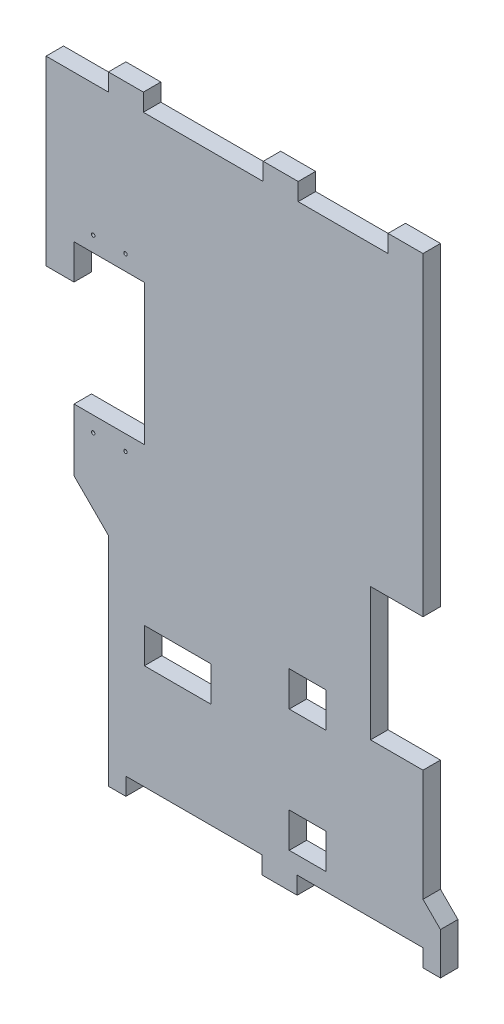
SolidWorks part; units mm, degrees
material "Balsa"
ref_plane "Plan de face" through (0, 0, 0) normal (0, 0, 1) x (1, 0, 0)
ref_plane "Plan de dessus" through (0, 0, 0) normal (0, 1, 0) x (1, 0, 0)
ref_plane "Plan de droite" through (0, 0, 0) normal (1, 0, 0) x (0, 0, -1)
sketch "Esquisse1" plane through (0, 0, 0) normal (0, 0, 1) x (1, 0, 0)
  line L0 (90, 82) -> (90, 167)
  line L1 (5, 0) -> (90, 0)
  line L2 (0, 0) -> (0, 167)
  line L3 (10, 167) -> (80, 167)
  line L4 (90, 0) -> (90, 44)
  line L5 (90, 82) -> (75, 82)
  line L6 (0, 167) -> (0, 172)
  line L7 (0, 172) -> (10, 172)
  line L8 (10, 167) -> (10, 172)
  line L9 (0, 0) -> (0, -5)
  line L10 (90, 167) -> (90, 172)
  line L11 (90, 172) -> (80, 172)
  line L12 (80, 167) -> (80, 172)
  line L13 (0, -5) -> (5, -5)
  line L14 (5, 0) -> (5, -5)
  line L16 (90, 44) -> (75, 44)
  line L17 (75, 82) -> (75, 44)
  line L18 (51.7344, 50) -> (62.2003, 50)
  line L19 (51.7344, 50) -> (51.7344, 40)
  line L20 (51.7344, 40) -> (62.2003, 40)
  line L25 (62.2003, 50) -> (62.2003, 40)
  line L32 (51.7344, 15) -> (62.2003, 15)
  line L34 (51.7344, 15) -> (51.7344, 5)
  line L35 (51.7344, 5) -> (62.2003, 5)
  line L37 (62.2003, 15) -> (62.2003, 5)
  line L54 (29.3073, 40) -> (10.2917, 40)
  line L55 (29.3073, 40) -> (29.3073, 30)
  line L56 (29.3073, 30) -> (10.2917, 30)
  line L57 (10.2917, 40) -> (10.2917, 30)
  dimension "D1" = 167
  dimension "D2" = 90
  dimension "D3" = 10
  dimension "D4" = 5
  dimension "D5" = 5
  dimension "D6" = 15
  dimension "D7" = 38
  dimension "D8" = 82
extrude "Boss.-Extru.1" add sketch "Esquisse1" along normal blind 5
sketch "Esquisse2" plane through (0, 0, 5) normal (0, 0, 1) x (1, 0, 0)
  line L0 (0, 172) -> (0, -5) construction
  line L1 (0, 167) -> (-9.8347, 167)
  line L2 (0, 167) -> (0, 57.1653)
  line L3 (0, 57.1653) -> (-9.8347, 67)
  line L4 (-9.8347, 167) -> (-9.8347, 67)
  line L6 (80, 167) -> (10, 167) construction
  dimension "D1" = 9.8347
  dimension "D2" = 135
  dimension "D3" = 100
extrude "Boss.-Extru.2" add sketch "Esquisse2" against normal blind 5
sketch "Esquisse3" plane through (0, 0, 0) normal (0, 0, -1) x (-1, 0, 0)
  line L0 (9.8347, 167) -> (9.8347, 67) construction
  line L1 (-10.3653, 125) -> (9.8347, 125)
  line L2 (-10.3653, 125) -> (-10.3653, 84.8)
  line L3 (-10.3653, 84.8) -> (9.8347, 84.8)
  line L4 (9.8347, 125) -> (9.8347, 84.8)
  line L5 (0, 167) -> (9.8347, 167) construction
  line L6 (4.3597, 129.4) -> (-4.8903, 129.4) construction
  line L7 (-4.8903, 129.4) -> (-4.8903, 80.4) construction
  line L8 (-4.8903, 80.4) -> (4.3597, 80.4) construction
  line L9 (9.8347, 167) -> (9.8347, 67) construction
  line L10 (-80, 167) -> (-10, 167) construction
  circle A0 centre (4.3597, 129.4) radius 0.5
  circle A1 centre (-4.8903, 129.4) radius 0.5
  circle A2 centre (4.3597, 80.4) radius 0.5
  circle A3 centre (-4.8903, 80.4) radius 0.5
  dimension "D9" = 1
  dimension "D1" = 17.8
  dimension "D2" = 42
  dimension "D3" = 20.2
  dimension "D4" = 9.25
  dimension "D5" = 9.25
  dimension "D6" = 49
  dimension "D7" = 14.725
  dimension "D8" = 37.6
extrude "Enlèv. mat.-Extru.1" cut sketch "Esquisse3" against normal blind 5
sketch "Esquisse4" plane through (0, 0, 5) normal (0, 0, 1) x (1, 0, 0)
  line L0 (-9.8347, 167) -> (-17.8347, 167)
  line L1 (-9.8347, 167) -> (-9.8347, 125) construction
  line L2 (-17.8347, 167) -> (-17.8347, 115)
  line L3 (-17.8347, 115) -> (-9.8347, 115)
  line L4 (-9.8347, 115) -> (-9.8347, 125)
  line L5 (-9.8347, 125) -> (-9.8347, 167)
  line L6 (0, 167) -> (-9.8347, 167) construction
  line L7 (5, 0) -> (90, 0) construction
  line L8 (44, 0) -> (54, 0)
  line L9 (44, 0) -> (44, -5)
  line L10 (44, -5) -> (54, -5)
  line L11 (54, 0) -> (54, -5)
  line L12 (0, 57.1653) -> (0, -5) construction
  line L13 (90, 0) -> (90, 44) construction
  line L14 (90, 12) -> (95, 7)
  line L15 (90, 12) -> (90, -5)
  line L16 (90, -5) -> (95, -5)
  line L17 (95, 7) -> (95, -5)
  line L18 (80, 167) -> (10, 167) construction
  line L19 (44.2889, 167) -> (54.2889, 167)
  line L20 (44.2889, 167) -> (44.2889, 172)
  line L21 (44.2889, 172) -> (54.2889, 172)
  line L22 (54.2889, 167) -> (54.2889, 172)
  line L23 (90, 82) -> (90, 172) construction
  dimension "D1" = 10
  dimension "D2" = 8
  dimension "D3" = 10
  dimension "D4" = 5
  dimension "D5" = 44
  dimension "D6" = 5
  dimension "D7" = 12
  dimension "D8" = 135
  dimension "D9" = 5
  dimension "D10" = 10
  dimension "D11" = 35.7111
extrude "Boss.-Extru.3" add sketch "Esquisse4" against normal blind 5
